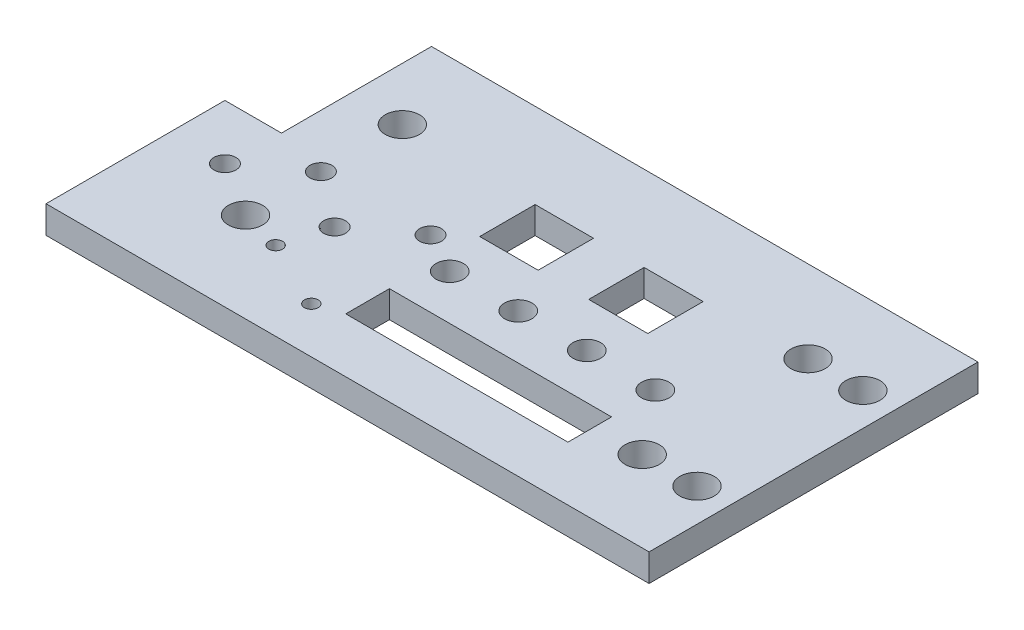
SolidWorks part; units mm, degrees
material "K110"
ref_plane "Front Plane" through (0, 0, 0) normal (0, 0, 1) x (1, 0, 0)
ref_plane "Top Plane" through (0, 0, 0) normal (0, 1, 0) x (1, 0, 0)
ref_plane "Right Plane" through (0, 0, 0) normal (1, 0, 0) x (0, 0, -1)
sketch "Sketch1" plane through (0, 0, 0) normal (0, 1, 0) x (1, 0, 0)
  line L1 (-110, -60) -> (110, -60)
  line L2 (-110, -60) -> (-110, 60)
  line L3 (-110, 60) -> (110, 60)
  line L4 (110, -60) -> (110, 60)
  line L5 (-110, -60) -> (110, 60) construction
  line L6 (-110, 60) -> (110, -60) construction
  point P0 (0, 0)
  dimension "D1" = 120
  dimension "D2" = 220
extrude "Boss-Extrude1" add sketch "Sketch1" against normal blind 10
sketch "Sketch2" plane through (0, 0, 0) normal (0, 1, 0) x (1, 0, 0)
  line L1 (-110, 60) -> (-89.3675, 60)
  line L2 (-110, 60) -> (-110, 5.27)
  line L3 (-110, 5.27) -> (-89.3675, 5.27)
  line L4 (-89.3675, 60) -> (-89.3675, 5.27)
  line L5 (-90, -14.72) -> (-89.3675, 5.27) construction
  line L10 (-70, 0.28) -> (-89.3675, 5.27) construction
  dimension "D1" = 20
extrude "Cut-Extrude1" cut sketch "Sketch2" against normal up to next
hole_wizard "Ø12.5 (12.5) Diameter Hole1" positions "Sketch5" profile "Sketch4" hole size "Ø12.5" standard "ISO" end condition through all
sketch "Sketch5" plane through (0, -10, 0) normal (0, -1, 0) x (-1, 0, 0)
  point P0 (-98, 30)
  point P3 (-78, 30)
  point P6 (70, 30)
  point P9 (-98, -30.5)
  point P12 (-78, -30.5)
  point P15 (70, -27.22)
sketch "Sketch4" plane through (98, -10, -30) normal (1, 0, 0) x (0, 0, -1)
  line L0 (0, 0) -> (0, 10)
  line L1 (0, 10) -> (6.25, 10)
  line L2 (6.25, 10) -> (6.25, 0)
  line L5 (6.25, 0) -> (0, 0)
  line L11 (0, -6.35) -> (0, 107.95) construction
  dimension "Thru Hole Dia." = 12.5
  dimension "Thru Hole Depth" = 10
hole_wizard "Ø10.0 (10) Diameter Hole1" positions "Sketch8" profile "Sketch7" hole size "Ø10.0" standard "ISO" end condition through all
sketch "Sketch8" plane through (0, -10, 0) normal (0, -1, 0) x (-1, 0, 0)
  point P0 (-60, -7.72)
  point P3 (-35, -7.72)
  point P6 (-10, -7.72)
  point P9 (15, -7.72)
sketch "Sketch7" plane through (60, -10, 7.72) normal (1, 0, 0) x (0, 0, -1)
  line L0 (0, 0) -> (0, 10)
  line L1 (0, 10) -> (5, 10)
  line L2 (5, 10) -> (5, 0)
  line L5 (5, 0) -> (0, 0)
  line L11 (0, -6.35) -> (0, 107.95) construction
  dimension "Thru Hole Dia." = 10
  dimension "Thru Hole Depth" = 10
hole_wizard "Ø5.0mm Dowel Hole1" positions "Sketch11" profile "Sketch10" hole size "Ø5.0" standard "ISO" end condition through all
sketch "Sketch11" plane through (0, -10, 0) normal (0, -1, 0) x (-1, 0, 0)
  point P0 (30, -43.22)
  point P3 (55, -31.22)
sketch "Sketch10" plane through (-30, -10, 43.22) normal (1, 0, 0) x (0, 0, -1)
  line L0 (0, 0) -> (0, 10)
  line L1 (0, 10) -> (2.5, 10)
  line L2 (2.5, 10) -> (2.5, 0)
  line L5 (2.5, 0) -> (0, 0)
  line L11 (0, -6.35) -> (0, 107.95) construction
  dimension "Thru Hole Dia." = 5
  dimension "Thru Hole Depth" = 10
sketch "Sketch12" plane through (0, -10, 0) normal (0, -1, 0) x (1, 0, 0)
  line L674 (60.5278, 40.1278) -> (60.5278, 24.1922) construction
  line L675 (60.5278, 24.1922) -> (-20.5278, 24.1922) construction
  line L676 (-20.5278, 40.1278) -> (60.5278, 40.1278) construction
  line L677 (-20.5278, 24.1922) -> (-20.5278, 40.1278) construction
  line L678 (60.5278, 40.1278) -> (60.5278, 24.1922)
  line L679 (60.5278, 24.1922) -> (-20.5278, 24.1922)
  line L680 (-20.5278, 40.1278) -> (60.5278, 40.1278)
  line L681 (-20.5278, 24.1922) -> (-20.5278, 40.1278)
  line L682 (-20.5278, -8.7522) -> (0.7778, -8.7522) construction
  line L683 (-20.5278, -28.9678) -> (-20.5278, -8.7522) construction
  line L684 (0.7778, -28.9678) -> (-20.5278, -28.9678) construction
  line L685 (0.7778, -8.7522) -> (0.7778, -28.9678) construction
  line L686 (19.2222, -28.9678) -> (19.2222, -8.7522) construction
  line L687 (40.7778, -28.9678) -> (19.2222, -28.9678) construction
  line L688 (40.7778, -8.7522) -> (40.7778, -28.9678) construction
  line L689 (19.2222, -8.7522) -> (40.7778, -8.7522) construction
  line L690 (-20.5278, -8.7522) -> (0.7778, -8.7522)
  line L691 (-20.5278, -28.9678) -> (-20.5278, -8.7522)
  line L692 (0.7778, -28.9678) -> (-20.5278, -28.9678)
  line L693 (0.7778, -8.7522) -> (0.7778, -28.9678)
  line L694 (19.2222, -28.9678) -> (19.2222, -8.7522)
  line L695 (40.7778, -28.9678) -> (19.2222, -28.9678)
  line L696 (40.7778, -8.7522) -> (40.7778, -28.9678)
  line L697 (19.2222, -8.7522) -> (40.7778, -8.7522)
  circle A0 centre (-90, 14.72) radius 4 construction
  circle A1 centre (-70, -0.28) radius 4 construction
  circle A2 centre (-50, 14.72) radius 4 construction
  circle A3 centre (-30, -0.28) radius 4 construction
  circle A4 centre (-90, 14.72) radius 4
  circle A5 centre (-70, -0.28) radius 4
  circle A6 centre (-50, 14.72) radius 4
  circle A7 centre (-30, -0.28) radius 4
extrude "Cut-Extrude2" cut sketch "Sketch12" against normal up to next
draft "Draft1" type of draft neutral plane draft angle 1 faces to draft 16 face at (60.5278, -5, 32.16) face at (20, -5, 40.1278) face at (-20.5278, -5, 32.16) face at (20, -5, 24.1922) face at (-9.875, -5, -8.7522) face at (30, -5, -8.7522) face at (40.7778, -5, -18.86) face at (0.7778, -5, -18.86) face at (-20.5278, -5, -18.86) face at (19.2222, -5, -18.86) face at (30, -5, -28.9678) face at (-9.875, -5, -28.9678) face at (-50, -10, 10.72) face at (-30, -10, -4.28) face at (-70, -10, -4.28) face at (-90, -10, 10.72) neutral plane through (0, 0, 0) neutral plane normal (0, 1, 0) reverse direction yes parameters "D1"=1
